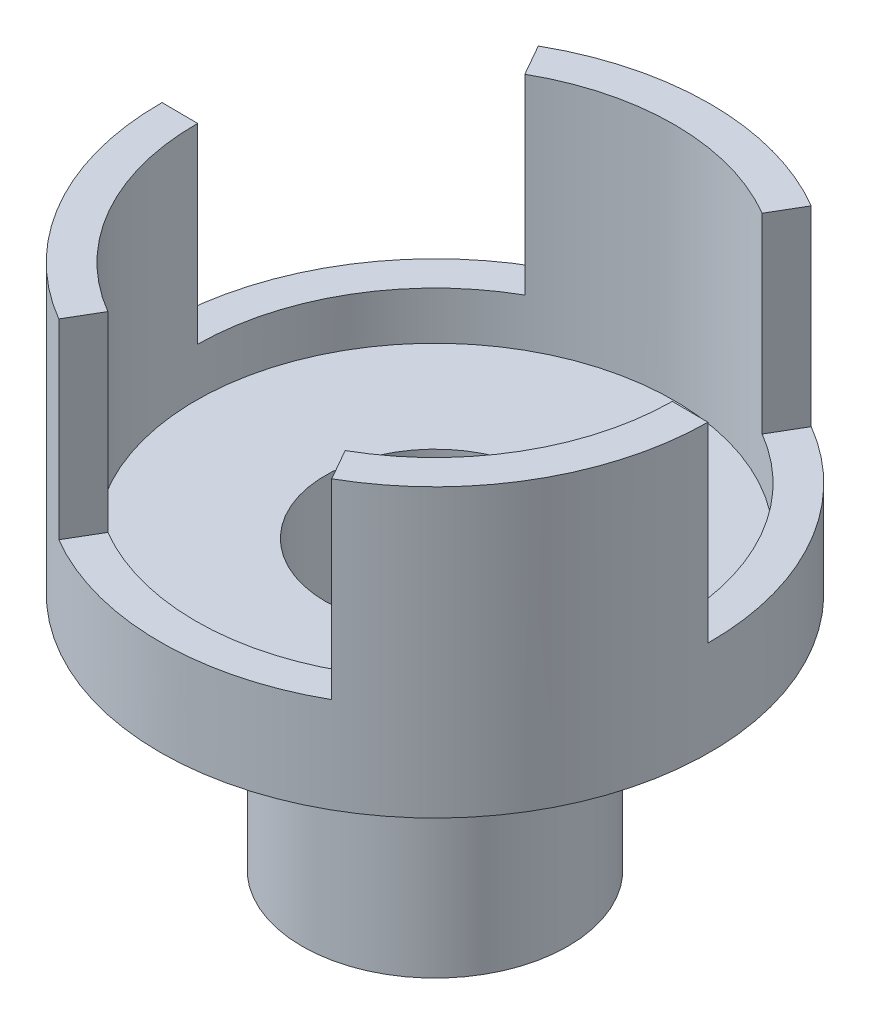
SolidWorks part; units mm, degrees
ref_plane "Front Plane" through (0, 0, 0) normal (0, 0, 1) x (1, 0, 0)
ref_plane "Top Plane" through (0, 0, 0) normal (0, 1, 0) x (1, 0, 0)
ref_plane "Right Plane" through (0, 0, 0) normal (1, 0, 0) x (0, 0, -1)
sketch "Sketch1" plane through (0, 0, 0) normal (0, 1, 0) x (1, 0, 0)
  circle A0 centre (0, 0) radius 10
  circle A1 centre (0, 0) radius 11.5
  dimension "D1" = 20
  dimension "D2" = 23
extrude "Boss-Extrude1" add sketch "Sketch1" along normal blind 10 contours A1 | A0
sketch "Sketch2" plane through (0, 0, 0) normal (0, -1, 0) x (1, 0, 0)
  circle A0 centre (0, 0) radius 11.5
  circle A1 centre (0, 0) radius 4.5757
  circle A2 centre (0, 0) radius 5.5584
  circle M1 centre (0, 0) radius 11.5
  circle M2 centre (0, 0) radius 10
extrude "Boss-Extrude3" add sketch "Sketch2" along normal blind 2 contours M1 M2 | A2 M2 region at (-11.1747, 0, 0) region at (-9.7172, 0, 0)
extrude "Boss-Extrude4" add sketch "Sketch2<3>" along normal blind 10 contours A2 A1 region at (-5.4012, 0, 0)
sketch "Sketch2<3>" plane through (0, 0, 0) normal (0, -1, 0) x (1, 0, 0) same geometry as "Sketch2"
sketch "Sketch3" plane through (0, -10, 0) normal (0, -1, 0) x (1, 0, 0)
  circle A0 centre (0, 0) radius 5.5584
extrude "Boss-Extrude5" add sketch "Sketch3" along normal blind 2
sketch "Sketch4" plane through (0, 10, 0) normal (0, 1, 0) x (1, 0, 0)
  line L0 (0, 0) -> (0, -10) construction
  line L2 (-5.8208, -9.9181) -> (0, 0) construction
  line L3 (5.6789, -10) -> (0, 0) construction
  line L4 (-5.8208, -9.9181) -> (-5.0616, -8.6244)
  line L5 (5.6789, -10) -> (4.9382, -8.6957)
  line L6 (-5.6789, 10) -> (-4.9382, 8.6957)
  line L7 (-11.4997, 0.0819) -> (-9.9997, 0.0712)
  line L8 (11.4997, -0.0819) -> (9.9997, -0.0712)
  line L9 (5.8208, 9.9181) -> (5.0616, 8.6244)
  circle A0 centre (0, 0) radius 10 construction
  circle A1 centre (0, 0) radius 11.5 construction
  arc A2 (-5.8208, -9.9181) -> (5.6789, -10) centre (0, 0) ccw
  circle A3 centre (0, 0) radius 10 construction
  arc A4 (4.9382, -8.6957) -> (-5.0616, -8.6244) centre (0, 0) cw
  arc A5 (-5.6789, 10) -> (-11.4997, 0.0819) centre (0, 0) ccw
  arc A6 (-9.9997, 0.0712) -> (-4.9382, 8.6957) centre (0, 0) cw
  arc A7 (11.4997, -0.0819) -> (5.8208, 9.9181) centre (0, 0) ccw
  arc A8 (5.0616, 8.6244) -> (9.9997, -0.0712) centre (0, 0) cw
  point P29 (0, 0)
  dimension "D1" = 60
  dimension "D2" = 3
extrude "Cut-Extrude1" cut sketch "Sketch4" against normal blind 8 contours L6 A6 L7 A5 | L4 A4 L5 A2 | L8 A8 L9 A7
